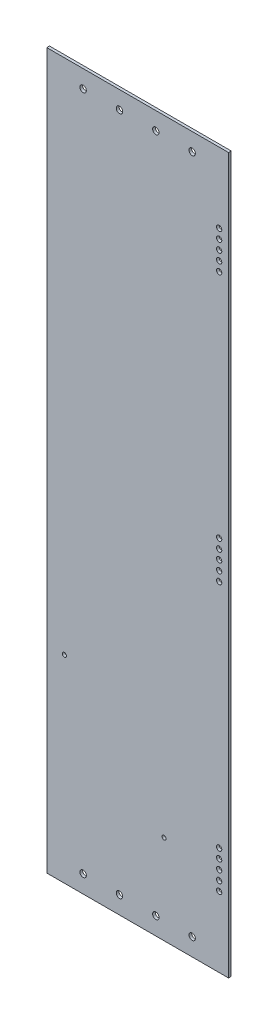
SolidWorks part; units mm, degrees
material "5052-H32"
ref_plane "Front Plane" through (0, 0, 0) normal (0, 0, 1) x (1, 0, 0)
ref_plane "Top Plane" through (0, 0, 0) normal (0, 1, 0) x (1, 0, 0)
ref_plane "Right Plane" through (0, 0, 0) normal (1, 0, 0) x (0, 0, -1)
sketch "Sketch1" plane through (0, 0, 0) normal (0, 0, 1) x (1, 0, 0)
  line L0 (55, 0) -> (-55, 0) construction
  line L1 (-77.5, 304.8) -> (77.5, 304.8)
  line L2 (-77.5, 304.8) -> (-77.5, -304.8)
  line L3 (-77.5, -304.8) -> (77.5, -304.8)
  line L4 (77.5, 304.8) -> (77.5, -304.8)
  line L5 (-77.5, 304.8) -> (77.5, -304.8) construction
  line L6 (-77.5, -304.8) -> (77.5, 304.8) construction
  point P0 (0, 0)
  point P5 (69.5, 244.8)
  point P7 (69.5, 228.8)
  point P8 (69.5, 236.8)
  point P9 (69.5, 220.8)
  point P10 (69.5, 212.8)
  point P11 (69.5, 8)
  point P12 (69.5, 16)
  point P13 (69.5, -212.8)
  point P14 (69.5, -228.8)
  point P15 (69.5, -220.8)
  point P16 (69.5, -236.8)
  point P17 (69.5, -244.8)
  point P18 (69.5, -8)
  point P19 (69.5, -16)
  point P20 (-46.5, 289.795)
  point P21 (-15.5, 289.795)
  point P22 (69.5, 0)
  point P23 (15.5, 289.795)
  point P24 (46.5, 289.795)
  point P25 (22.5, -228.6)
  point P26 (-62.5, -136.1)
  point P29 (46.5, -289.795)
  point P30 (15.5, -289.795)
  point P31 (-15.5, -289.795)
  point P32 (-46.5, -289.795)
  dimension "D1" = 609.6
  dimension "D2" = 155
  dimension "D3" = 8
  dimension "D4" = 60
  dimension "D5" = 8
  dimension "D6" = 8
  dimension "D7" = 8
  dimension "D8" = 8
  dimension "D9" = 60
  dimension "D10" = 8
  dimension "D11" = 8
  dimension "D12" = 8
  dimension "D13" = 8
  dimension "D14" = 8
  dimension "D15" = 8
  dimension "D16" = 8
  dimension "D17" = 8
  dimension "D18" = 8
  dimension "D19" = 8
  dimension "D20" = 31
  dimension "D21" = 31
  dimension "D22" = 31
  dimension "D23" = 31
  dimension "D24" = 15.005
  dimension "D25" = 92.5
  dimension "D26" = 85
  dimension "D27" = 76.2
  dimension "D28" = 15
extrude "Boss-Extrude1" add sketch "Sketch1" along normal blind 2.305
hole_wizard "M4 Clearance Hole1" positions "Sketch3" profile "Sketch5" hole size "M4" standard "ANSI Metric" end condition through all
sketch "Sketch3" plane through (0, 0, 2.305) normal (0, 0, 1) x (1, 0, 0)
  point P4 (69.5, 228.8)
  point P9 (69.5, 244.8)
  point P12 (69.5, 236.8)
  point P15 (69.5, 220.8)
  point P18 (69.5, 212.8)
  point P21 (69.5, 16)
  point P24 (69.5, 8)
  point P27 (69.5, 0)
  point P30 (69.5, -8)
  point P33 (69.5, -16)
  point P36 (69.5, -212.8)
  point P39 (69.5, -220.8)
  point P42 (69.5, -228.8)
  point P45 (69.5, -236.8)
  point P48 (69.5, -244.8)
sketch "Sketch5" plane through (69.5, 228.8, 2.305) normal (1, 0, 0) x (0, -1, 0)
  line L0 (0, 0) -> (0, 2.305)
  line L1 (0, 2.305) -> (2.25, 2.305)
  line L2 (2.25, 2.305) -> (2.25, 0)
  line L5 (2.25, 0) -> (0, 0)
  line L11 (0, -6.35) -> (0, 107.95) construction
  dimension "Thru Hole Dia." = 4.5
  dimension "Thru Hole Depth" = 2.305
hole_wizard "M5 Clearance Hole1" positions "Sketch6" profile "Sketch7" hole size "M5" standard "ANSI Metric" end condition through all
sketch "Sketch6" plane through (0, 0, 2.305) normal (0, 0, 1) x (1, 0, 0)
  point P0 (-46.5, -289.795)
  point P3 (-15.5, -289.795)
  point P6 (15.5, -289.795)
  point P9 (46.5, -289.795)
  point P12 (-46.5, 289.795)
  point P15 (-15.5, 289.795)
  point P18 (15.5, 289.795)
  point P21 (46.5, 289.795)
sketch "Sketch7" plane through (-46.5, -289.795, 2.305) normal (1, 0, 0) x (0, -1, 0)
  line L0 (0, 0) -> (0, 2.305)
  line L1 (0, 2.305) -> (2.75, 2.305)
  line L2 (2.75, 2.305) -> (2.75, 0)
  line L5 (2.75, 0) -> (0, 0)
  line L11 (0, -6.35) -> (0, 107.95) construction
  dimension "Thru Hole Dia." = 5.5
  dimension "Thru Hole Depth" = 2.305
hole_wizard "Ø3.5 (3.5) Diameter Hole1" positions "Sketch8" profile "Sketch9" hole size "Ø3.5" standard "ANSI Metric" end condition through all
sketch "Sketch8" plane through (0, 0, 0) normal (0, 0, -1) x (-1, 0, 0)
  point P0 (-22.5, -228.6)
  point P3 (62.5, -136.1)
sketch "Sketch9" plane through (22.5, -228.6, 0) normal (1, 0, 0) x (0, 1, 0)
  line L0 (0, 0) -> (0, 2.305)
  line L1 (0, 2.305) -> (1.75, 2.305)
  line L2 (1.75, 2.305) -> (1.75, 0)
  line L5 (1.75, 0) -> (0, 0)
  line L11 (0, -6.35) -> (0, 107.95) construction
  dimension "Thru Hole Dia." = 3.5
  dimension "Thru Hole Depth" = 2.305
